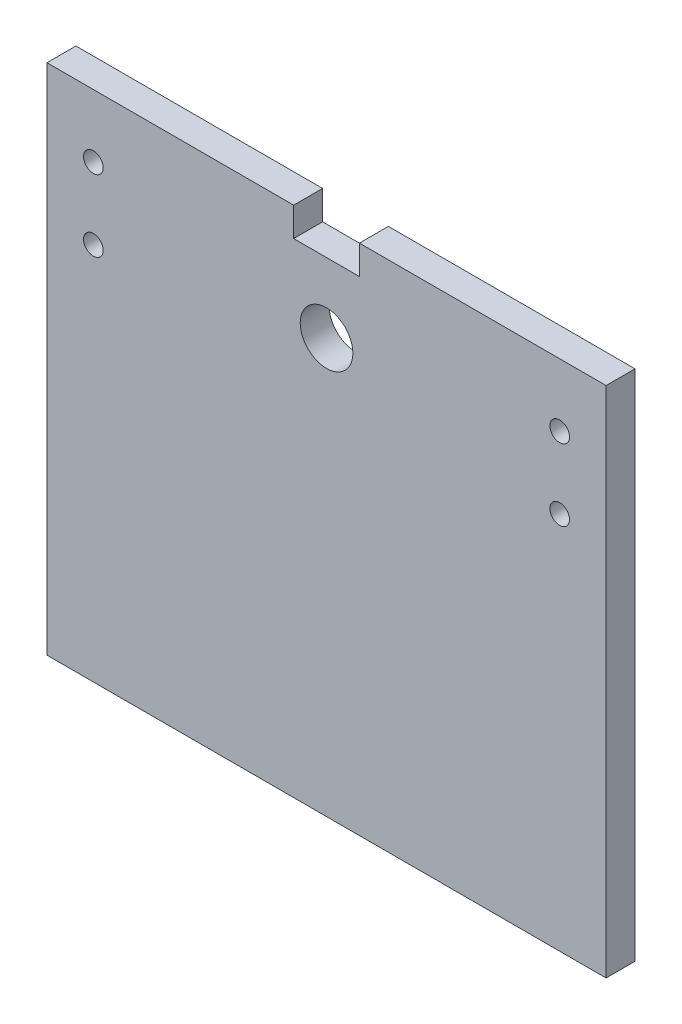
SolidWorks part; units mm, degrees
ref_plane "Front Plane" through (0, 0, 0) normal (0, 0, 1) x (1, 0, 0)
ref_plane "Top Plane" through (0, 0, 0) normal (0, 1, 0) x (1, 0, 0)
ref_plane "Right Plane" through (0, 0, 0) normal (1, 0, 0) x (0, 0, -1)
sketch "Sketch1" plane through (0, 0, 0) normal (0, 0, 1) x (1, 0, 0)
  line L0 (-6.35, 49.53) -> (-6.35, 43.942)
  line L1 (-53.975, -49.53) -> (53.975, -49.53)
  line L2 (-53.975, -49.53) -> (-53.975, 49.53)
  line L3 (-53.975, 49.53) -> (-6.35, 49.53)
  line L4 (53.975, -49.53) -> (53.975, 49.53)
  line L5 (-53.975, -49.53) -> (53.975, 49.53) construction
  line L6 (-53.975, 49.53) -> (53.975, -49.53) construction
  line L7 (-6.35, 43.942) -> (6.35, 43.942)
  line L8 (6.35, 43.942) -> (6.35, 49.53)
  line L9 (6.35, 49.53) -> (53.975, 49.53)
  point P0 (0, 0)
  dimension "D1" = 107.95
  dimension "D2" = 99.06
  dimension "D3" = 5.588
  dimension "D4" = 12.7
extrude "Boss-Extrude1" add sketch "Sketch1" along normal mid plane 5.588
sketch "Sketch2" plane through (0, 0, -2.794) normal (0, 0, -1) x (-1, 0, 0)
  point P0 (-45.0148, 37.3948)
  point P1 (-45.0148, 23.5652)
  point P3 (45.0148, 37.3948)
  point P5 (45.0148, 23.5652)
hole_wizard "#6 Clearance Hole1" positions "Sketch3" profile "Sketch4" hole size "#6" standard "ANSI Inch" end condition through all
sketch "Sketch3" plane through (0, 0, -2.794) normal (0, 0, -1) x (-1, 0, 0)
  point P0 (-45.0148, 37.3948)
  point P3 (-45.0148, 23.5652)
  point P6 (45.0148, 37.3948)
  point P9 (45.0148, 23.5652)
sketch "Sketch4" plane through (45.0148, 37.3948, -2.794) normal (1, 0, 0) x (0, 1, 0)
  line L0 (0, 0) -> (0, 5.588)
  line L1 (0, 5.588) -> (1.8986, 5.588)
  line L2 (1.8986, 5.588) -> (1.8986, 0)
  line L5 (1.8986, 0) -> (0, 0)
  line L11 (0, -6.35) -> (0, 107.95) construction
  dimension "Thru Hole Dia." = 3.7973
  dimension "Thru Hole Depth" = 5.588
sketch "Sketch5" plane through (0, 0, -2.794) normal (0, 0, -1) x (-1, 0, 0)
  line L0 (53.975, 49.53) -> (53.975, -49.53) construction
  line L1 (53.975, -49.53) -> (-53.975, -49.53) construction
  circle A0 centre (0, 30.48) radius 5.08
  point P2 (0, 0)
  dimension "D1" = 10.16
  dimension "D2" = 53.975
  dimension "D3" = 80.01
extrude "Cut-Extrude1" cut sketch "Sketch5" against normal up to next
